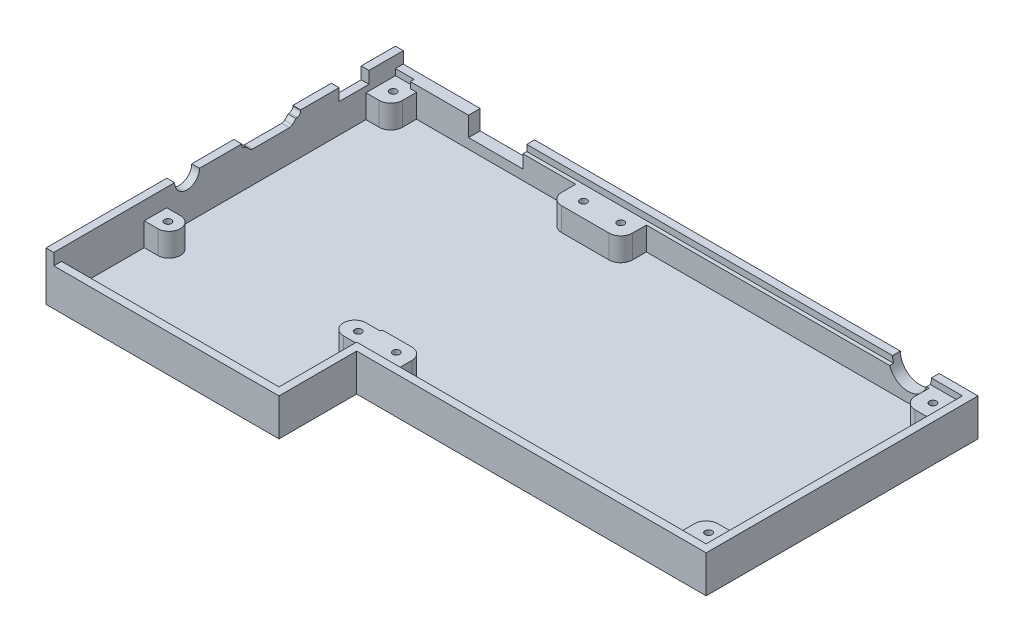
SolidWorks part; units mm, degrees
ref_plane "Front Plane" through (0, 0, 0) normal (0, 0, 1) x (1, 0, 0)
ref_plane "Top Plane" through (0, 0, 0) normal (0, 1, 0) x (1, 0, 0)
ref_plane "Right Plane" through (0, 0, 0) normal (1, 0, 0) x (0, 0, -1)
sketch "Sketch1" plane through (0, 0, 0) normal (0, 1, 0) x (1, 0, 0)
  line L1 (30, -45) -> (-30, -45)
  line L2 (30, -45) -> (30, 45)
  line L3 (30, 45) -> (-30, 45)
  line L4 (-30, -45) -> (-30, 45)
  line L5 (30, -45) -> (-30, 45) construction
  line L6 (30, 45) -> (-30, -45) construction
  point P0 (0, 0)
  dimension "D1" = 60
  dimension "D2" = 90
extrude "Boss-Extrude1" add sketch "Sketch1" along normal blind 2
sketch "Sketch2" plane through (0, 2, 0) normal (0, 1, 0) x (1, 0, 0)
  line L0 (30, -45) -> (30, 45) construction
  line L1 (30, -45) -> (30, 45)
  line L2 (-30, 45) -> (-30, -45) construction
  line L3 (-30, -45) -> (30, -45) construction
  line L4 (30, 45) -> (-30, 45) construction
  line L5 (-30, 45) -> (-30, -45)
  line L6 (-30, -45) -> (30, -45)
  line L7 (30, 45) -> (-30, 45)
  line L8 (28, -43) -> (28, 43)
  line L9 (28, 43) -> (-28, 43)
  line L10 (-28, 43) -> (-28, -43)
  line L11 (-28, -43) -> (28, -43)
  dimension "D1" = 2
extrude "Boss-Extrude2" add sketch "Sketch2" along normal blind 10.6
sketch "Sketch3" plane through (0, 12.6, 0) normal (0, 1, 0) x (1, 0, 0)
  line L1 (-28, -43) -> (28, -43)
  line L2 (-28, -43) -> (-28, -45)
  line L3 (-28, -45) -> (30, -45)
  line L6 (30, 45) -> (-30, 45) construction
  line L7 (-28, 43) -> (28, 43)
  line L8 (-28, 43) -> (-28, 45)
  line L9 (-28, 45) -> (30, 45)
  line L11 (28, -43) -> (28, 43) construction
  line L13 (28, 43) -> (28, -43)
  line L15 (30, 45) -> (30, -45)
extrude "Cut-Extrude1" cut sketch "Sketch3" against normal blind 3
sketch "Sketch15" plane through (0, 0, 0) normal (0, -1, 0) x (1, 0, 0)
  line L1 (30, -45) -> (120, -45)
  line L2 (30, -45) -> (30, 25)
  line L3 (30, 25) -> (120, 25)
  line L4 (120, -45) -> (120, 25)
  dimension "D1" = 90
  dimension "D2" = 70
extrude "Boss-Extrude6" add sketch "Sketch15" against normal up to surface (2 mm away) up to face at (0, 2, 0)
sketch "Sketch16" plane through (0, 2, 0) normal (0, 1, 0) x (1, 0, 0)
  line L0 (118, 43) -> (30, 43)
  line L2 (30, -23) -> (118, -23)
  line L3 (118, -23) -> (118, 43)
  line L4 (30, 45) -> (30, -25)
  line L5 (30, -25) -> (120, -25)
  line L6 (120, -25) -> (120, 45)
  line L7 (120, 45) -> (30, 45)
  line L9 (30, -25) -> (120, -25)
  line L10 (120, -25) -> (120, 45)
  line L11 (120, 45) -> (30, 45)
  line L12 (30, 45) -> (30, 43)
  line L13 (30, -23) -> (30, -25)
  dimension "D2" = 88
  dimension "D3" = 66
  dimension "D4" = 2
  dimension "D5" = 66
  dimension "D1" = 0
extrude "Boss-Extrude7" add sketch "Sketch16" along normal up to surface (7.6 mm away) up to face at (0.5, 9.6, 0)
sketch "Sketch4" plane through (0, 2, 0) normal (0, 1, 0) x (1, 0, 0)
  line L0 (27, -21.7) -> (27, -42)
  line L1 (120, 45) -> (-28, 45) construction
  line L2 (30, -45) -> (30, 45) construction
  line L3 (-28, 43) -> (-28, -43) construction
  line L4 (116.4, 42) -> (30, 42)
  line L5 (27, 42) -> (27, -15.9)
  line L6 (-28, -43) -> (28, -43) construction
  line L7 (27, -42) -> (-28, -42)
  line L8 (27, -21.7) -> (23.3, -21.7)
  line L9 (28, -45) -> (28, 45) construction
  line L10 (23.3, -15.9) -> (27, -15.9)
  line L11 (19.4, 42) -> (19.4, 38.4)
  line L12 (22.4, 35.4) -> (27, 35.4)
  line L13 (-21.6, 43) -> (-21.6, 38.4)
  line L14 (-24.6, 35.4) -> (-28, 35.4)
  line L15 (-28, 45) -> (-28, -45) construction
  line L16 (-28, -15.9) -> (-24.5, -15.9)
  line L17 (28, 43) -> (-28, 43) construction
  line L18 (-24.5, -21.7) -> (-28, -21.7)
  line L19 (24.2, -15.9) -> (24.2, -21.7) construction
  line L20 (5.8, 42) -> (5.8, 43)
  line L21 (5.8, 42) -> (27, 42)
  line L23 (30, -22) -> (116.4, -22)
  line L24 (116.4, -22) -> (116.4, 42)
  line L25 (-28, 43) -> (28, 43) construction
  line L26 (118, -23) -> (118, 43)
  line L28 (30, 43) -> (30, -23)
  line L29 (118, -23) -> (118, 43)
  line L34 (30, -23) -> (30, 43) construction
  line L35 (30, -22) -> (30, -23)
  line L36 (30, -23) -> (30, 43) construction
  line L37 (30, 43) -> (30, 42)
  line L38 (37.6, 42) -> (37.6, 38.9)
  line L39 (34.1, 35.4) -> (30, 35.4)
  line L40 (110.3, 42) -> (110.3, 38.9)
  line L41 (113.8, 35.4) -> (116.4, 35.4)
  line L42 (110.3, -22) -> (110.3, -18.9)
  line L43 (113.3, -15.9) -> (116.4, -15.9)
  line L44 (37.1, -22) -> (37.1, -18.9)
  line L45 (34.1, -15.9) -> (30, -15.9)
  line L51 (118, 43) -> (30, 43)
  line L53 (118, 43) -> (30, 43)
  line L54 (30, -23) -> (118, -23)
  line L55 (30, -23) -> (118, -23)
  circle A0 centre (24.2, 39.2) radius 0.9
  circle A1 centre (-24.8, 39.2) radius 0.9
  circle A2 centre (24.2, -18.8) radius 0.9
  circle A3 centre (-24.8, -18.8) radius 0.9
  arc A4 (23.3, -15.9) -> (23.3, -21.7) centre (23.3, -18.8) ccw
  arc A5 (-24.5, -15.9) -> (-24.5, -21.7) centre (-24.5, -18.8) cw
  arc A6 (19.4, 38.4) -> (22.4, 35.4) centre (22.4, 38.4) ccw
  arc A7 (-21.6, 38.4) -> (-24.6, 35.4) centre (-24.6, 38.4) cw
  circle A8 centre (32.8, 39.2) radius 0.9
  circle A9 centre (32.8, -18.8) radius 0.9
  circle A10 centre (113.6, 39.2) radius 0.9
  circle A11 centre (113.6, -18.8) radius 0.9
  arc A12 (110.3, -18.9) -> (113.3, -15.9) centre (113.3, -18.9) cw
  arc A13 (37.1, -18.9) -> (34.1, -15.9) centre (34.1, -18.9) ccw
  arc A14 (110.3, 38.9) -> (113.8, 35.4) centre (113.8, 38.9) ccw
  arc A15 (37.6, 38.9) -> (34.1, 35.4) centre (34.1, 38.9) cw
  point P43 (5.8, 42.5)
  point P50 (19.4, 35.4)
  point P55 (-21.6, 35.4)
  point P92 (110.3, 35.4)
  point P95 (37.6, 35.4)
  line M18 (-28, -43) -> (28, -43)
  line M19 (28, -43) -> (28, 43)
  line M20 (28, 43) -> (-28, 43)
  line M21 (-28, 43) -> (-28, -43)
  dimension "D3" = 1.8
  dimension "D6" = 3.7
  dimension "D8" = 2.9
  dimension "D12" = 2.9
  dimension "D13" = 5.8
  dimension "D17" = 3
  dimension "D22" = 3
  dimension "D33" = 3
  dimension "D34" = 3
  dimension "D1" = 5.8
  dimension "D2" = 5.8
  dimension "D4" = 49
  dimension "D5" = 58
  dimension "D7" = 5.8
  dimension "D9" = 1
  dimension "D10" = 3.5
  dimension "D11" = 5.8
  dimension "D14" = 1
  dimension "D15" = 0
  dimension "D16" = 7.6
  dimension "D18" = 1
  dimension "D19" = 7.6
  dimension "D20" = 7.6
  dimension "D21" = 6.4
  dimension "D23" = 22.2
  dimension "D24" = 21.2
  dimension "D25" = 1
  dimension "D26" = 86.4
  dimension "D27" = 1
  dimension "D28" = 7.6
  dimension "D29" = 1
  dimension "D30" = 86.4
  dimension "D31" = 2.8
  dimension "D32" = 2.8
extrude "Boss-Extrude3" add sketch "Sketch4" along normal blind 6 contours L10 L19 A2 L8 L0 L7 L20 L21 L5 M21 M18 M19 M20 | L19 L10 A4 L8 A2 | A5 L16 L18 A3 M21 | A7 L13 L14 A1 M20 M21 | L11 A6 L12 L5 L21 A0 region at (25.6, 2, 20.6737) region at (22.4509, 2, 18.8) region at (-27.9136, 2, 18.8) region at (-27.9006, 2, -39.2) region at (23.2766, 2, -38.7833)
sketch "Sketch18" plane through (0, 9.6, 0) normal (0, 1, 0) x (1, 0, 0)
  line L0 (118, -23) -> (30, -23) construction
  line L1 (28, 43) -> (30, 43)
  line L2 (28, 43) -> (28, -23)
  line L3 (28, -23) -> (30, -23)
  line L4 (30, 43) -> (30, -23)
  line L5 (30, -23) -> (30, 43) construction
extrude "Cut-Extrude11" cut sketch "Sketch18" against normal up to surface (1.6 mm away) up to face at (24.2, 8, 19.7)
sketch "Sketch7" plane through (0, 2, 0) normal (0, 1, 0) x (1, 0, 0)
  line L0 (5.8, 43) -> (-21.6, 43) construction
  line L1 (5.8, 42) -> (-8.2, 42)
  line L2 (5.8, 42) -> (5.8, 43)
  line L3 (5.8, 43) -> (-8.2, 43)
  line L4 (-8.2, 42) -> (-8.2, 43)
  dimension "D1" = 14
extrude "Boss-Extrude4" add sketch "Sketch7" along normal blind 2.6
sketch "Sketch8" plane through (0, 9.6, 0) normal (0, 1, 0) x (1, 0, 0)
  line L0 (-28, 43) -> (118, 43) construction
  line L1 (5.8, 43) -> (-8.2, 43)
  line L2 (5.8, 43) -> (5.8, 45)
  line L3 (5.8, 45) -> (-8.2, 45)
  line L4 (-8.2, 43) -> (-8.2, 45)
  line L5 (120, 45) -> (-28, 45) construction
  line L6 (5.8, 42) -> (5.8, 43) construction
  line L7 (-8.2, 42) -> (5.8, 42) construction
extrude "Cut-Extrude2" cut sketch "Sketch8" against normal up to surface (5 mm away) up to face at (-1.2, 4.6, -42.5)
sketch "Sketch9" plane through (0, 2, 0) normal (0, 1, 0) x (1, 0, 0)
  line L1 (-8.2, 42) -> (-23.2, 42)
  line L2 (-8.2, 42) -> (-8.2, 43)
  line L3 (-8.2, 43) -> (-23.2, 43)
  line L4 (-23.2, 42) -> (-23.2, 43)
  line L5 (-8.2, 43) -> (-21.6, 43) construction
  dimension "D1" = 15
extrude "Boss-Extrude5" add sketch "Sketch9" along normal up to surface (7.6 mm away)
sketch "Sketch10" plane through (0, 12.6, 0) normal (0, 1, 0) x (1, 0, 0)
  line L0 (-30, 45) -> (-30, -45) construction
  line L1 (-30, 36.17) -> (-28, 36.17)
  line L2 (-30, 36.17) -> (-30, 28.47)
  line L3 (-30, 28.47) -> (-28, 28.47)
  line L4 (-28, 36.17) -> (-28, 28.47)
  line L5 (-28, 45) -> (-28, -45) construction
  line L6 (-28, 45) -> (-30, 45) construction
  point P10 (-29, 28.47)
  point P11 (-29, 36.17)
  dimension "D1" = 8.83
  dimension "D2" = 7.7
extrude "Cut-Extrude3" cut sketch "Sketch10" against normal blind 3.1
sketch "Sketch11" plane through (0, 12.6, 0) normal (0, 1, 0) x (1, 0, 0)
  line L5 (-30, 28.47) -> (-30, -45) construction
  line L6 (-30, 3.38) -> (-28, 3.38)
  line L7 (-30, 3.38) -> (-30, 18.58)
  line L8 (-30, 18.58) -> (-28, 18.58)
  line L9 (-28, 3.38) -> (-28, 18.58)
  line L10 (-28, 28.47) -> (-28, -45) construction
  line L11 (-30, 28.47) -> (-28, 28.47) construction
  dimension "D1" = 9.89
  dimension "D2" = 15.2
extrude "Cut-Extrude4" cut sketch "Sketch11" against normal blind 1.22
sketch "Sketch12" plane through (0, 11.38, 0) normal (0, 1, 0) x (1, 0, 0)
  line L0 (-28, 3.38) -> (-28, 18.58) construction
  line L5 (-30, 18.58) -> (-30, 3.38) construction
  line L10 (-30, 4.6) -> (-28, 4.6)
  line L11 (-30, 4.6) -> (-30, 17.36)
  line L12 (-30, 17.36) -> (-28, 17.36)
  line L13 (-28, 4.6) -> (-28, 17.36)
  line L14 (-28, 18.58) -> (-30, 18.58) construction
  line L15 (-30, 3.38) -> (-28, 3.38) construction
  dimension "D1" = 1.22
  dimension "D2" = 1.22
extrude "Cut-Extrude6" cut sketch "Sketch12" against normal blind 1.32
sketch "Sketch13" plane through (-28, 0, 0) normal (1, 0, 0) x (0, 0, -1)
  line L0 (3.38, 12.6) -> (-45, 12.6) construction
  line L1 (-13.88, 12.6) -> (-7.48, 12.6)
  arc A0 (-7.48, 12.6) -> (-13.88, 12.6) centre (-10.68, 12.6) cw
  dimension "D3" = 3.2
  dimension "D1" = 6.4
  dimension "D2" = 10.86
extrude "Cut-Extrude7" cut sketch "Sketch13" against normal up to next
fillet "Fillet6" radius 1 2 edges at (-29, 11.38, -3.38) (-29, 11.38, -18.58)
chamfer "Chamfer2" distance 1.22 angle 45 2 edges at (-29, 10.06, -17.36) (-29, 10.06, -4.6)
fillet "Fillet7" radius 1 4 edges at (-29, 10.06, -16.14) (-29, 10.06, -5.82) (-29, 11.38, -4.6) (-29, 11.38, -17.36)
sketch "Sketch19" plane through (0, 2, 0) normal (0, 1, 0) x (1, 0, 0)
  line L0 (117, 42) -> (31, 42)
  line L1 (31, 42) -> (31, -22)
  line L2 (31, -22) -> (117, -22)
  line L3 (117, -22) -> (117, 42)
  line L4 (118, -23) -> (118, 43)
  line L5 (118, 43) -> (30, 43)
  line L6 (30, 43) -> (30, -23)
  line L7 (30, -23) -> (118, -23)
  line L8 (118, -23) -> (118, 43)
  line L9 (118, 43) -> (30, 43)
  line L10 (30, 43) -> (30, -23)
  line L11 (30, -23) -> (118, -23)
  line L12 (37.6, 42) -> (37.6, 38.4)
  line L13 (34.6, 35.4) -> (31, 35.4)
  line L14 (110.4, 42) -> (110.4, 38.4)
  line L15 (113.4, 35.4) -> (117, 35.4)
  line L16 (117, -15.4) -> (113.4, -15.4)
  line L17 (110.4, -18.4) -> (110.4, -22)
  line L18 (31, -15.4) -> (34.6, -15.4)
  line L19 (37.6, -18.4) -> (37.6, -22)
  circle A0 centre (33.8, 39.2007) radius 0.9
  circle A1 centre (114.2, 39.2007) radius 0.9
  circle A2 centre (114.2, -18.58) radius 0.9
  circle A3 centre (33.8, -18.58) radius 0.9
  arc A4 (34.6, -15.4) -> (37.6, -18.4) centre (34.6, -18.4) cw
  arc A5 (113.4, -15.4) -> (110.4, -18.4) centre (113.4, -18.4) ccw
  arc A6 (110.4, 38.4) -> (113.4, 35.4) centre (113.4, 38.4) ccw
  arc A7 (37.6, 38.4) -> (34.6, 35.4) centre (34.6, 38.4) cw
  point P32 (37.6, -15.4)
  point P35 (110.4, -15.4)
  line M17 (118, -23) -> (118, 43)
  line M18 (118, 43) -> (30, 43)
  line M19 (30, 43) -> (30, -23)
  line M20 (30, -23) -> (118, -23)
  dimension "D3" = 1.8
  dimension "D10" = 3
  dimension "D4" = 2.8
  dimension "D5" = 3.42
  dimension "D6" = 2.7993
  dimension "D7" = 2.8
  dimension "D8" = 6.6
  dimension "D9" = 6.6
  dimension "D1" = 0
  dimension "D2" = 1
extrude "Boss-Extrude9" add sketch "Sketch19" along normal up to surface (6 mm away) contours A4 L18 L1 L2 L19 A3 | L16 A5 L17 L2 L3 A2 | L14 A6 L15 L3 L0 A1 | A7 L12 L0 L1 L13 A0 | L3 L2 L1 L0 M20 M17 M18 M19 region at (116.9067, 2, -38.7) region at (37.5067, 2, -40.2) region at (116.9067, 2, 18.7) region at (32.8, 2, 15.4933) region at (74, 2, 22.89) up to face at (24.2, 8, 19.7)
sketch "Sketch20" plane through (0, 8, 0) normal (0, 1, 0) x (1, 0, 0)
  line L1 (27, 35.4) -> (31, 35.4)
  line L2 (27, 35.4) -> (27, -15.4)
  line L3 (27, -15.4) -> (31, -15.4)
  line L4 (31, 35.4) -> (31, -15.4)
extrude "Cut-Extrude12" cut sketch "Sketch20" against normal up to surface (6 mm away) up to face at (-0.7222, 2, -3.7087)
fillet "Fillet8" radius 0.5 1 edges at (27, 5, 15.9)
fillet "Fillet9" radius 0.5 1 edges at (27, 5, 15.4)
sketch "Sketch21" plane through (0, 0, -45) normal (0, 0, -1) x (-1, 0, 0)
  line L0 (-120, 9.6) -> (-5.8, 9.6) construction
  line L1 (-120, 9.6) -> (-120, 0) construction
  line L2 (-110, 9.6) -> (-100, 9.6)
  arc A0 (-110, 9.6) -> (-100, 9.6) centre (-105, 9.6) ccw
  dimension "D1" = 5
  dimension "D2" = 10
  dimension "D3" = 10
extrude "Cut-Extrude13" cut sketch "Sketch21" against normal blind 10
